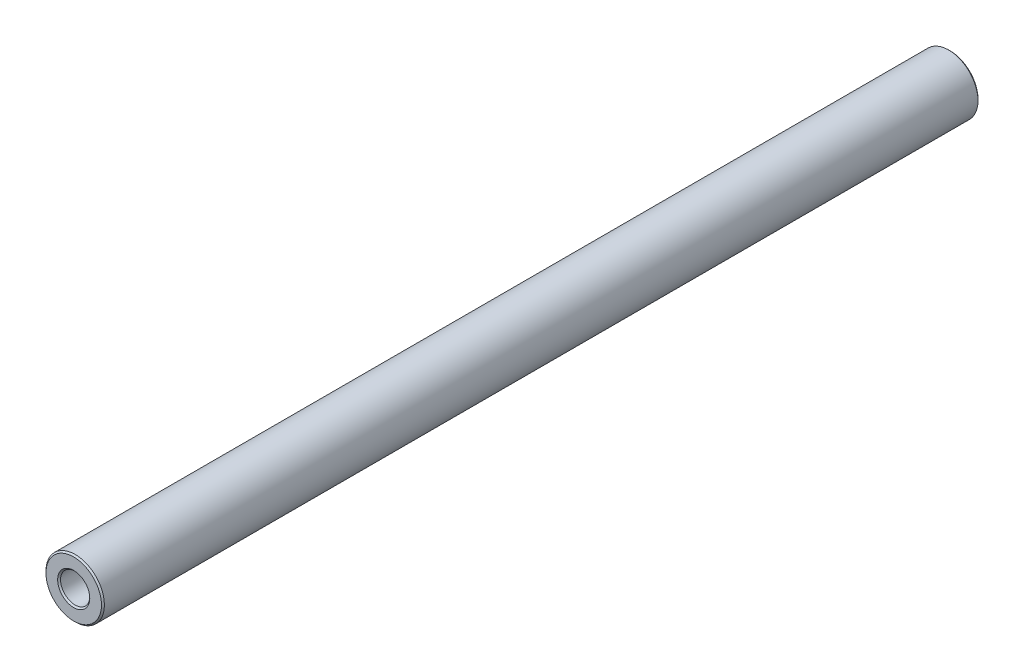
SolidWorks part; units mm, degrees
material "AISI 316 Annealed Stainless Steel Bar (SS)"
ref_plane "Front Plane" through (0, 0, 0) normal (0, 0, 1) x (1, 0, 0)
ref_plane "Top Plane" through (0, 0, 0) normal (0, 1, 0) x (1, 0, 0)
ref_plane "Right Plane" through (0, 0, 0) normal (1, 0, 0) x (0, 0, -1)
other "Table"
sketch "Sketch1" plane through (0, 0, 0) normal (0, 0, 1) x (1, 0, 0)
  circle A0 centre (0, 0) radius 5
  circle A1 centre (0, 0) radius 2.5
  dimension "OD" = 10
  dimension "ID" = 5
extrude "Boss-Extrude1" add sketch "Sketch1" along normal mid plane 150
chamfer "Chamfer1" distance 0.25 angle 45 4 edges at (2.5, 0, -75) (2.5, 0, 75) (5, 0, -75) (5, 0, 75)
